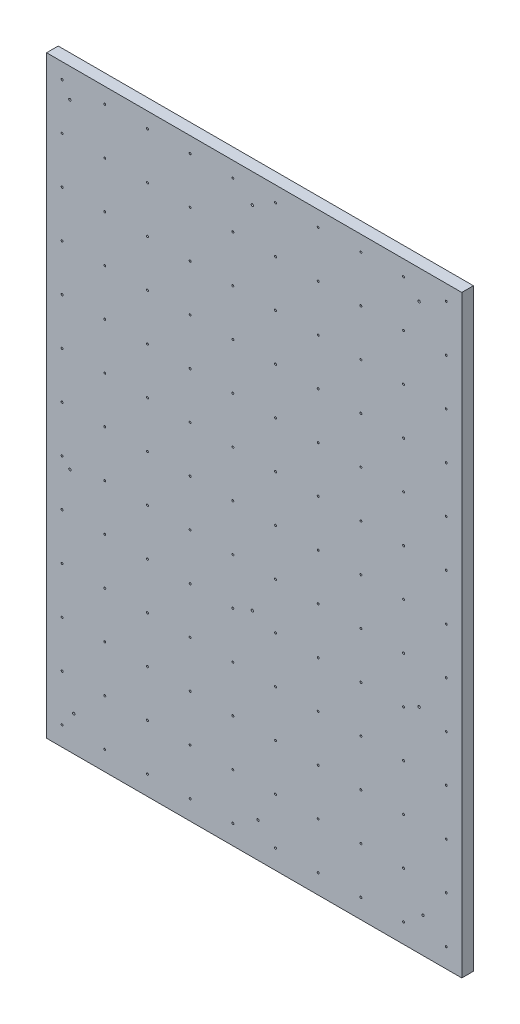
SolidWorks part; units mm, degrees
material "Фанера, берёза, ФСФ ВВ/С ГОСТ 3916.1-96"
ref_plane "Спереди" through (0, 0, 0) normal (0, 0, 1) x (1, 0, 0)
ref_plane "Сверху" through (0, 0, 0) normal (0, 1, 0) x (1, 0, 0)
ref_plane "Справа" through (0, 0, 0) normal (1, 0, 0) x (0, 0, -1)
sketch "Эскиз1" plane through (0, 0, 0) normal (0, 0, 1) x (1, 0, 0)
  line L1 (-535, 765) -> (535, 765)
  line L2 (-535, 765) -> (-535, -765)
  line L3 (-535, -765) -> (535, -765)
  line L4 (535, 765) -> (535, -765)
  line L5 (0, -765) -> (0, 765) construction
  line L6 (-535, 0) -> (535, 0) construction
  point P0 (0, 0)
  dimension "D1" = 1070
  dimension "D2" = 1530
extrude "Бобышка-Вытянуть1" add sketch "Эскиз1" along normal mid plane 30
sketch "Эскиз2" plane through (0, 0, 15) normal (0, 0, 1) x (1, 0, 0)
  line L0 (-535, 765) -> (-535, -765) construction
  line L1 (535, 765) -> (-535, 765) construction
  line L2 (-495, 725) -> (-385, 725) construction
  circle A0 centre (-495, 725) radius 2.5
  circle A1 centre (-385, 725) radius 2.5
  circle A2 centre (-275, 725) radius 2.5
  circle A3 centre (-165, 725) radius 2.5
  circle A4 centre (-55, 725) radius 2.5
  circle A5 centre (55, 725) radius 2.5
  circle A6 centre (165, 725) radius 2.5
  circle A7 centre (275, 725) radius 2.5
  circle A8 centre (385, 725) radius 2.5
  circle A9 centre (495, 725) radius 2.5
  circle A10 centre (-385, 605) radius 2.5
  circle A11 centre (-275, 605) radius 2.5
  circle A12 centre (-165, 605) radius 2.5
  circle A13 centre (-55, 605) radius 2.5
  circle A14 centre (55, 605) radius 2.5
  circle A15 centre (165, 605) radius 2.5
  circle A16 centre (275, 605) radius 2.5
  circle A17 centre (385, 605) radius 2.5
  circle A18 centre (495, 605) radius 2.5
  circle A19 centre (-385, 485) radius 2.5
  circle A20 centre (-275, 485) radius 2.5
  circle A21 centre (-165, 485) radius 2.5
  circle A22 centre (-55, 485) radius 2.5
  circle A23 centre (55, 485) radius 2.5
  circle A24 centre (165, 485) radius 2.5
  circle A25 centre (275, 485) radius 2.5
  circle A26 centre (385, 485) radius 2.5
  circle A27 centre (495, 485) radius 2.5
  circle A28 centre (-385, 365) radius 2.5
  circle A29 centre (-275, 365) radius 2.5
  circle A30 centre (-165, 365) radius 2.5
  circle A31 centre (-55, 365) radius 2.5
  circle A32 centre (55, 365) radius 2.5
  circle A33 centre (165, 365) radius 2.5
  circle A34 centre (275, 365) radius 2.5
  circle A35 centre (385, 365) radius 2.5
  circle A36 centre (495, 365) radius 2.5
  circle A37 centre (-385, 245) radius 2.5
  circle A38 centre (-275, 245) radius 2.5
  circle A39 centre (-165, 245) radius 2.5
  circle A40 centre (-55, 245) radius 2.5
  circle A41 centre (55, 245) radius 2.5
  circle A42 centre (165, 245) radius 2.5
  circle A43 centre (275, 245) radius 2.5
  circle A44 centre (385, 245) radius 2.5
  circle A45 centre (495, 245) radius 2.5
  circle A46 centre (-385, 125) radius 2.5
  circle A47 centre (-275, 125) radius 2.5
  circle A48 centre (-165, 125) radius 2.5
  circle A49 centre (-55, 125) radius 2.5
  circle A50 centre (55, 125) radius 2.5
  circle A51 centre (165, 125) radius 2.5
  circle A52 centre (275, 125) radius 2.5
  circle A53 centre (385, 125) radius 2.5
  circle A54 centre (495, 125) radius 2.5
  circle A55 centre (-385, 5) radius 2.5
  circle A56 centre (-275, 5) radius 2.5
  circle A57 centre (-165, 5) radius 2.5
  circle A58 centre (-55, 5) radius 2.5
  circle A59 centre (55, 5) radius 2.5
  circle A60 centre (165, 5) radius 2.5
  circle A61 centre (275, 5) radius 2.5
  circle A62 centre (385, 5) radius 2.5
  circle A63 centre (495, 5) radius 2.5
  circle A64 centre (-385, -115) radius 2.5
  circle A65 centre (-275, -115) radius 2.5
  circle A66 centre (-165, -115) radius 2.5
  circle A67 centre (-55, -115) radius 2.5
  circle A68 centre (55, -115) radius 2.5
  circle A69 centre (165, -115) radius 2.5
  circle A70 centre (275, -115) radius 2.5
  circle A71 centre (385, -115) radius 2.5
  circle A72 centre (495, -115) radius 2.5
  circle A73 centre (-385, -235) radius 2.5
  circle A74 centre (-275, -235) radius 2.5
  circle A75 centre (-165, -235) radius 2.5
  circle A76 centre (-55, -235) radius 2.5
  circle A77 centre (55, -235) radius 2.5
  circle A78 centre (165, -235) radius 2.5
  circle A79 centre (275, -235) radius 2.5
  circle A80 centre (385, -235) radius 2.5
  circle A81 centre (495, -235) radius 2.5
  circle A82 centre (-385, -355) radius 2.5
  circle A83 centre (-275, -355) radius 2.5
  circle A84 centre (-165, -355) radius 2.5
  circle A85 centre (-55, -355) radius 2.5
  circle A86 centre (55, -355) radius 2.5
  circle A87 centre (165, -355) radius 2.5
  circle A88 centre (275, -355) radius 2.5
  circle A89 centre (385, -355) radius 2.5
  circle A90 centre (495, -355) radius 2.5
  circle A91 centre (-385, -475) radius 2.5
  circle A92 centre (-275, -475) radius 2.5
  circle A93 centre (-165, -475) radius 2.5
  circle A94 centre (-55, -475) radius 2.5
  circle A95 centre (55, -475) radius 2.5
  circle A96 centre (165, -475) radius 2.5
  circle A97 centre (275, -475) radius 2.5
  circle A98 centre (385, -475) radius 2.5
  circle A99 centre (495, -475) radius 2.5
  circle A100 centre (-385, -595) radius 2.5
  circle A101 centre (-275, -595) radius 2.5
  circle A102 centre (-165, -595) radius 2.5
  circle A103 centre (-55, -595) radius 2.5
  circle A104 centre (55, -595) radius 2.5
  circle A105 centre (165, -595) radius 2.5
  circle A106 centre (275, -595) radius 2.5
  circle A107 centre (385, -595) radius 2.5
  circle A108 centre (495, -595) radius 2.5
  circle A109 centre (-385, -715) radius 2.5
  circle A110 centre (-275, -715) radius 2.5
  circle A111 centre (-165, -715) radius 2.5
  circle A112 centre (-55, -715) radius 2.5
  circle A113 centre (55, -715) radius 2.5
  circle A114 centre (165, -715) radius 2.5
  circle A115 centre (275, -715) radius 2.5
  circle A116 centre (385, -715) radius 2.5
  circle A117 centre (495, -715) radius 2.5
  circle A118 centre (-495, 605) radius 2.5
  circle A119 centre (-495, 485) radius 2.5
  circle A120 centre (-495, 365) radius 2.5
  circle A121 centre (-495, 245) radius 2.5
  circle A122 centre (-495, 125) radius 2.5
  circle A123 centre (-495, 5) radius 2.5
  circle A124 centre (-495, -115) radius 2.5
  circle A125 centre (-495, -235) radius 2.5
  circle A126 centre (-495, -355) radius 2.5
  circle A127 centre (-495, -475) radius 2.5
  circle A128 centre (-495, -595) radius 2.5
  circle A129 centre (-495, -715) radius 2.5
  dimension "D1" = 5
  dimension "D2" = 40
  dimension "D3" = 40
  dimension "D6" = 110
  dimension "D4" = 10
  dimension "D5" = 13
extrude "Вырез-Вытянуть1" cut sketch "Эскиз2" against normal through all
sketch "Эскиз3" plane through (0, 0, 15) normal (0, 0, 1) x (1, 0, 0)
  circle A0 centre (-475, 690) radius 3 construction
  circle A1 centre (-5, 690) radius 3 construction
  circle A2 centre (425, 690) radius 3 construction
  circle A3 centre (-475, -135) radius 3 construction
  circle A4 centre (-5, -215) radius 3 construction
  circle A5 centre (425, -215) radius 3 construction
  circle A6 centre (-475, 690) radius 3
  circle A7 centre (-5, 690) radius 3
  circle A8 centre (425, 690) radius 3
  circle A9 centre (-475, -135) radius 3
  circle A10 centre (-5, -215) radius 3
  circle A11 centre (425, -215) radius 3
extrude "Вырез-Вытянуть2" cut sketch "Эскиз3" against normal through all
sketch "Эскиз4" plane through (0, 0, 15) normal (0, 0, 1) x (1, 0, 0)
  circle A0 centre (435, -675) radius 3 construction
  circle A1 centre (10, -675) radius 3 construction
  circle A2 centre (-465, -675) radius 3 construction
  circle A3 centre (435, -675) radius 3
  circle A4 centre (10, -675) radius 3
  circle A5 centre (-465, -675) radius 3
extrude "Вырез-Вытянуть3" cut sketch "Эскиз4" against normal through all
equation "\"ширина 1-я панель\"=1145"
equation "\"толщина дсп\"=30"
equation "\"D1@Эскиз1\"=\"ширина 2-я панель\""
equation "\"D3@Эскиз2\"=\"D2@Эскиз2\""
equation "\"длина панелей\"=1530"
equation "\"ширина 2-я панель\"=1070"
equation "\"D2@Эскиз1\"=\"длина панелей\""
